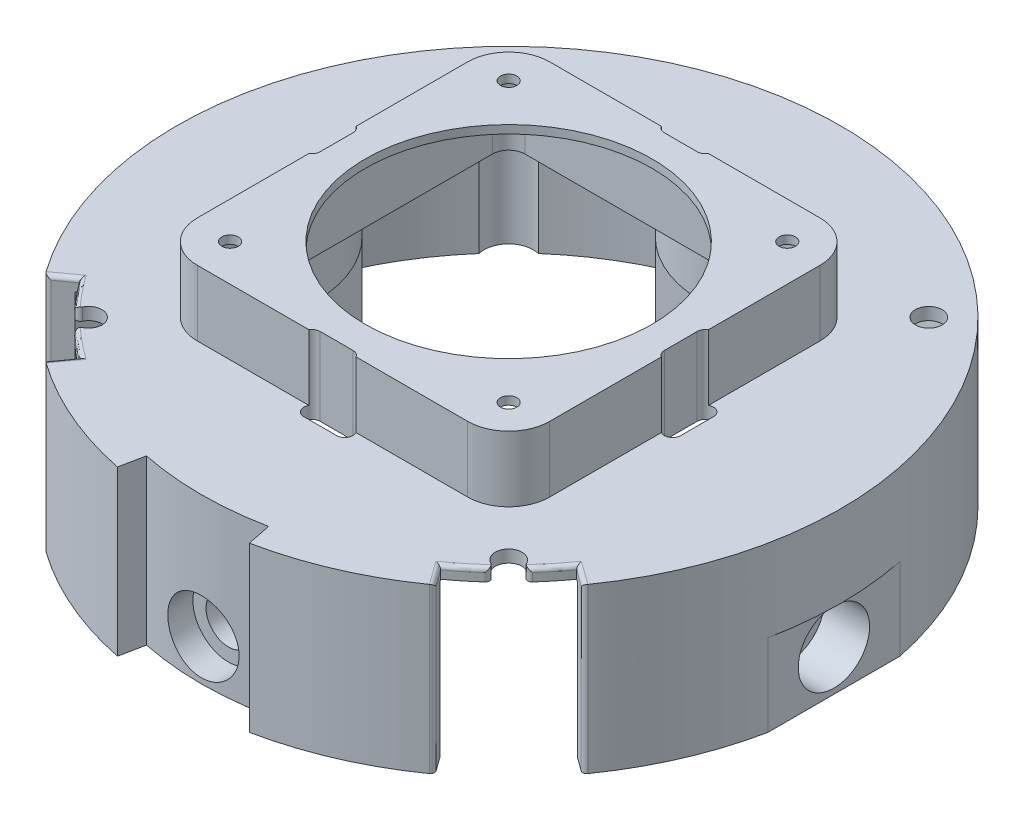
SolidWorks part; units mm, degrees
ref_plane "Front" through (0, 0, 0) normal (0, 0, 1) x (1, 0, 0)
ref_plane "Top" through (0, 0, 0) normal (0, 1, 0) x (1, 0, 0)
ref_plane "Right" through (0, 0, 0) normal (1, 0, 0) x (0, 0, -1)
sketch "Sketch1" plane through (0, 0, 0) normal (0, 1, 0) x (1, 0, 0)
  circle A0 centre (0, 0) radius 41.9
  dimension "D1" = 83.8
extrude "Top-Part" add sketch "Sketch1" along normal blind 15
sketch "Sketch2" plane through (0, 15, 0) normal (0, 1, 0) x (1, 0, 0)
  circle A0 centre (0, 0) radius 30
  dimension "D1" = 60
extrude "Cut-Extrude1" cut sketch "Sketch2" against normal blind 20
fillet "Fillet1" radius 1.5 1 edges at (0, 15, 41.9)
chamfer "Chamfer1" distance 2 angle 45 1 edges at (0, 15, 30)
sketch "Sketch8" plane through (0, 15, 0) normal (0, 1, 0) x (1, 0, 0)
  line L0 (0, 0) -> (0, 52.711) construction
  line L1 (25.0832, 22.5168) -> (28.0563, 23.5989)
  line L8 (0, 0) -> (-43.3951, 43.3951) construction
  line L9 (-25.6326, 25.6326) -> (-25.6326, 34.5059) construction
  line L10 (-22.5168, 25.0832) -> (-23.5989, 28.0563)
  line L11 (-23.5989, 28.0563) -> (-26.7147, 28.6057)
  line L12 (-26.7147, 28.6057) -> (-28.7485, 26.182)
  line L13 (-28.7485, 26.182) -> (-27.6663, 23.2089)
  line L14 (-27.6663, 23.2089) -> (-24.5505, 22.6595)
  line L15 (-24.5505, 22.6595) -> (-22.5168, 25.0832)
  line L16 (28.0563, 23.5989) -> (28.6057, 26.7147)
  line L17 (28.6057, 26.7147) -> (26.182, 28.7485)
  line L18 (26.182, 28.7485) -> (23.2089, 27.6663)
  line L19 (23.2089, 27.6663) -> (22.6595, 24.5505)
  line L20 (22.6595, 24.5505) -> (25.0832, 22.5168)
  line L21 (0, 0) -> (43.3951, 43.3951) construction
  line L23 (22.5168, -25.0832) -> (23.5989, -28.0563)
  line L24 (23.5989, -28.0563) -> (26.7147, -28.6057)
  line L25 (26.7147, -28.6057) -> (28.7485, -26.182)
  line L26 (28.7485, -26.182) -> (27.6663, -23.2089)
  line L27 (27.6663, -23.2089) -> (24.5505, -22.6595)
  line L28 (24.5505, -22.6595) -> (22.5168, -25.0832)
  line L29 (0, 0) -> (43.3951, -43.3951) construction
  line L31 (-25.0832, -22.5168) -> (-28.0563, -23.5989)
  line L32 (-28.0563, -23.5989) -> (-28.6057, -26.7147)
  line L33 (-28.6057, -26.7147) -> (-26.182, -28.7485)
  line L34 (-26.182, -28.7485) -> (-23.2089, -27.6663)
  line L35 (-23.2089, -27.6663) -> (-22.6595, -24.5505)
  line L36 (-22.6595, -24.5505) -> (-25.0832, -22.5168)
  line L37 (0, 0) -> (-43.3951, -43.3951) construction
  line L39 (-25.6326, 25.6326) -> (-27.9138, 12.6954) construction
  circle A0 centre (0, 0) radius 36.25 construction
  circle A1 centre (25.6326, 25.6326) radius 2.74 construction
  circle A2 centre (-25.6326, 25.6326) radius 2.74 construction
  circle A3 centre (25.6326, -25.6326) radius 2.74 construction
  circle A4 centre (-25.6326, -25.6326) radius 2.74 construction
  circle A5 centre (-25.6326, 25.6326) radius 1.625
  circle A6 centre (25.6326, 25.6326) radius 1.625
  circle A7 centre (25.6326, -25.6326) radius 1.625
  circle A8 centre (-25.6326, -25.6326) radius 1.625
  point P8 (25.6326, 25.6326)
  point P10 (28.331, 25.1568)
  point P18 (-25.6326, 25.6326)
  point P20 (-25.1568, 28.331)
  point P36 (25.6326, -25.6326)
  point P38 (25.1568, -28.331)
  point P50 (-25.6326, -25.6326)
  point P52 (-28.331, -25.1568)
  point P63 (0, 0)
  point P69 (-27.8231, 23.2366)
  dimension "D1" = 72.5
  dimension "D5" = 3.25
  dimension "D2" = 4
  dimension "D3" = 45
  dimension "D4" = 10
  dimension "D6" = 5.75
extrude "Cut-Extrude8" cut sketch "Sketch8<7>" against normal blind 3
sketch "Sketch8<7>" plane through (0, 15, 0) normal (0, 1, 0) x (1, 0, 0) same geometry as "Sketch8"
extrude "Cut-Extrude7" cut sketch "Sketch8" against normal through all contours A5 | A6 | A7 | A8
sketch "Sketch13" plane through (0, 0, 0) normal (0, -1, 0) x (1, 0, 0)
  line L0 (0, 0) -> (0, 66.0162) construction
  line L1 (-10, 35.5191) -> (-10, 40.6892)
  line L2 (10, 35.5191) -> (10, 40.6892)
  line L3 (-10, 40.6892) -> (10, 35.5191) construction
  line L4 (10, 40.6892) -> (-10, 35.5191) construction
  circle A0 centre (0, 0) radius 41.9 construction
  arc A1 (10, 40.6892) -> (-10, 40.6892) centre (0, 0) ccw
  arc A2 (10, 35.5191) -> (-10, 35.5191) centre (0, 0) ccw
  point P6 (0, 38.1042)
  point P10 (0, 36.9)
  point P12 (0, 41.9)
  dimension "D1" = 10
  dimension "D3" = 5
extrude "Cut-Extrude11" cut sketch "Sketch13" against normal through all
ref_plane "Plane2" through (0, 0, 41.9) normal (0, 0, 1) x (1, 0, 0)
ref_plane "Plane3" through (0, 0, 32.4) normal (0, 0, 1) x (1, 0, 0)
sketch "Sketch15" plane through (0, 0, 32.4) normal (0, 0, 1) x (1, 0, 0)
  line L0 (0, -23.0183) -> (0, 33.1182) construction
  circle A1 centre (0, 7.5) radius 1.625
  point P11 (0, 7.5)
  dimension "D3" = 3.25
  dimension "D1" = 7.5
extrude "Cut-Extrude14" cut sketch "Sketch15" against normal blind 10 and the other way blind 10
sketch "Sketch16" plane through (0, 0, 32.4) normal (0, 0, 1) x (1, 0, 0)
  line L0 (0, 0) -> (0, 26.985) construction
  line L2 (3.3775, 7.5) -> (1.6887, 10.425)
  line L3 (1.6887, 10.425) -> (-1.6887, 10.425)
  line L4 (-1.6887, 10.425) -> (-3.3775, 7.5)
  line L5 (-3.3775, 7.5) -> (-1.6887, 4.575)
  line L6 (-1.6887, 4.575) -> (1.6887, 4.575)
  line L7 (1.6887, 4.575) -> (3.3775, 7.5)
  circle A0 centre (0, 7.5) radius 2.925 construction
  point P4 (0, 4.575)
  point P13 (0, 10.425)
  dimension "D1" = 5.85
  dimension "D2" = 7.5
extrude "Cut-Extrude15" cut sketch "Sketch16" against normal blind 10
pattern_circular "CirPattern1" count 4 over 360 about axis through (0, 0, 0) along (0, 1, 0) of "Cut-Extrude14"
pattern_circular "CirPattern2" count 4 every 90 about axis through (0, 0, 0) along (0, 1, 0) of "Cut-Extrude15"
sketch "Sketch3" plane through (0, 0, 0) normal (0, -1, 0) x (1, 0, 0)
  circle A0 centre (0, 0) radius 41.9
  dimension "D1" = 83.8
extrude "Bottom-Part" add sketch "Sketch3" along normal blind 20 separate body
ref_plane "Plane1" through (0, -1.5, 0) normal (0, 1, 0) x (1, 0, 0)
sketch "Sketch6" plane through (0, -1.5, 0) normal (0, 1, 0) x (1, 0, 0)
  line L0 (0, 0) -> (-97.4577, 0) construction
  line L5 (-37.9, 0) -> (-41.9, 0) construction
  circle A0 centre (0, 0) radius 37.9
  circle A1 centre (0, 0) radius 41.9 construction
  circle A2 centre (0, 0) radius 41.9 construction
  point P6 (-37.9, 0)
  point P9 (-41.9, 0)
  dimension "D1" = 4
extrude "Cut-Extrude3" cut sketch "Sketch6" against normal through all
sketch "ｽｹｯﾁ1" plane through (0, 0, 0) normal (0, 1, 0) x (1, 0, 0)
  line L3 (21.5, -21.5) -> (-21.5, -21.5)
  line L4 (21.5, -21.5) -> (21.5, 21.5)
  line L5 (21.5, 21.5) -> (-21.5, 21.5)
  line L6 (-21.5, -21.5) -> (-21.5, 21.5)
  line L7 (21.5, -21.5) -> (-21.5, 21.5) construction
  line L8 (21.5, 21.5) -> (-21.5, -21.5) construction
  point P2 (0, 0)
  dimension "D1" = 43
extrude "ﾎﾞｽ - 押し出し1" add sketch "ｽｹｯﾁ1" along normal blind 8
fillet "ﾌｨﾚｯﾄ1" radius 5 4 edges at (21.5, 4, -21.5) (-21.5, 4, -21.5) (-21.5, 4, 21.5) (21.5, 4, 21.5)
sketch "Sketch7" plane through (0, -1.5, 0) normal (0, 1, 0) x (1, 0, 0)
  circle A0 centre (0, 0) radius 17.5
  circle A1 centre (17, -17) radius 1
  circle A2 centre (-17, -17) radius 1
  circle A3 centre (-17, 17) radius 1
  circle A4 centre (17, 17) radius 1
  dimension "D1" = 35
  dimension "D2" = 2
extrude "Cut-Extrude4" cut sketch "Sketch7" against normal through all and the other way through all
sketch "Sketch12" plane through (0, -1.5, 0) normal (0, -1, 0) x (1, 0, 0)
  line L1 (19.75, -19.75) -> (-19.75, -19.75)
  line L2 (19.75, -19.75) -> (19.75, 19.75)
  line L3 (19.75, 19.75) -> (-19.75, 19.75)
  line L4 (-19.75, -19.75) -> (-19.75, 19.75)
  line L5 (19.75, -19.75) -> (-19.75, 19.75) construction
  line L6 (19.75, 19.75) -> (-19.75, -19.75) construction
  point P0 (0, 0)
  dimension "D1" = 39.5
extrude "Cut-Extrude10" cut sketch "Sketch12" against normal blind 8.5
fillet "Fillet3" radius 2 4 edges at (-19.75, 2.75, -19.75) (-19.75, 2.75, 19.75) (19.75, 2.75, -19.75) (19.75, 2.75, 19.75)
sketch "Sketch17" plane through (0, -1.5, 0) normal (0, -1, 0) x (1, 0, 0)
  circle A0 centre (25.6326, -25.6326) radius 1.625 construction
  circle A1 centre (-25.6326, -25.6326) radius 1.625 construction
  circle A2 centre (25.6326, 25.6326) radius 1.625 construction
  circle A3 centre (-25.6326, 25.6326) radius 1.625 construction
  circle A4 centre (25.6326, -25.6326) radius 1.625
  circle A5 centre (-25.6326, -25.6326) radius 1.625
  circle A6 centre (25.6326, 25.6326) radius 1.625
  circle A7 centre (-25.6326, 25.6326) radius 1.625
extrude "Cut-Extrude16" cut sketch "Sketch17" against normal through all
sketch "Sketch18" plane through (0, -1.5, 0) normal (0, -1, 0) x (1, 0, 0)
  circle A0 centre (-25.6326, 25.6326) radius 3
  circle A1 centre (25.6326, 25.6326) radius 3
  circle A2 centre (25.6326, -25.6326) radius 3
  circle A3 centre (-25.6326, -25.6326) radius 3
  dimension "D1" = 6
extrude "Cut-Extrude17" cut sketch "Sketch18" along normal through all
sketch "Sketch19" plane through (0, -1.5, 0) normal (0, -1, 0) x (1, 0, 0)
  arc A1 (35.4434, 13.423) -> (35.4434, -13.423) centre (37, 0) ccw
  arc A2 (35.4434, -13.423) -> (35.4434, 13.423) centre (0, 0) ccw
  arc A14 (-13.423, 35.4434) -> (13.423, 35.4434) centre (0, 37) ccw
  arc A15 (24.9276, 28.5486) -> (-24.9276, 28.5486) centre (0, 0) ccw construction
  arc A16 (13.423, 35.4434) -> (-13.423, 35.4434) centre (0, 0) ccw
  arc A17 (13.423, -35.4434) -> (-13.423, -35.4434) centre (0, -37) ccw
  arc A18 (-13.423, -35.4434) -> (13.423, -35.4434) centre (0, 0) ccw
  arc A19 (-35.4434, -13.423) -> (-35.4434, 13.423) centre (-37, 0) ccw
  arc A20 (-35.4434, 13.423) -> (-35.4434, -13.423) centre (0, 0) ccw
  dimension "D1" = 37
  dimension "D2" = 4
extrude "Boss-Extrude1" add sketch "Sketch19" along normal blind 8.5
sketch "Sketch23" plane through (0, -10, 0) normal (0, -1, 0) x (1, 0, 0)
  line L1 (9.7077, -27.6) -> (-9.7077, -27.6)
  line L2 (27.6, -9.7077) -> (27.6, 9.7077)
  line L3 (9.7077, 27.6) -> (-9.7077, 27.6)
  line L4 (-27.6, -9.7077) -> (-27.6, 9.7077)
  line L5 (27.6, -27.6) -> (-27.6, 27.6) construction
  line L6 (27.6, 27.6) -> (-27.6, -27.6) construction
  arc A0 (-13.423, -35.4434) -> (13.423, -35.4434) centre (0, 0) ccw construction
  arc A1 (-28.5486, 24.9276) -> (-28.5486, -24.9276) centre (0, 0) ccw construction
  arc A2 (13.423, 35.4434) -> (-13.423, 35.4434) centre (0, 0) ccw construction
  arc A3 (35.4434, -13.423) -> (35.4434, 13.423) centre (0, 0) ccw construction
  arc A4 (35.4434, 13.423) -> (35.4434, -13.423) centre (37, 0) ccw construction
  arc A5 (13.423, -35.4434) -> (-13.423, -35.4434) centre (0, -37) ccw construction
  arc A6 (-35.4434, -13.423) -> (-35.4434, 13.423) centre (-37, 0) ccw construction
  arc A7 (-13.423, 35.4434) -> (13.423, 35.4434) centre (0, 37) ccw construction
  arc A8 (-13.423, -35.4434) -> (13.423, -35.4434) centre (0, 0) ccw
  arc A9 (-35.4434, 13.423) -> (-35.4434, -13.423) centre (0, 0) ccw
  arc A10 (13.423, 35.4434) -> (-13.423, 35.4434) centre (0, 0) ccw
  arc A11 (35.4434, -13.423) -> (35.4434, 13.423) centre (0, 0) ccw
  arc A12 (35.4434, 13.423) -> (27.6, 9.7077) centre (37, 0) ccw
  arc A13 (13.423, -35.4434) -> (9.7077, -27.6) centre (0, -37) ccw
  arc A14 (-35.4434, -13.423) -> (-27.6, -9.7077) centre (-37, 0) ccw
  arc A15 (-13.423, 35.4434) -> (-9.7077, 27.6) centre (0, 37) ccw
  arc A16 (27.6, -9.7077) -> (35.4434, -13.423) centre (37, 0) ccw
  arc A17 (9.7077, 27.6) -> (13.423, 35.4434) centre (0, 37) ccw
  arc A18 (-27.6, 9.7077) -> (-35.4434, 13.423) centre (-37, 0) ccw
  arc A19 (-9.7077, -27.6) -> (-13.423, -35.4434) centre (0, -37) ccw
  point P0 (0, 0)
  dimension "D1" = 55.2
  dimension "D2" = 55.2
extrude "Boss-Extrude2" add sketch "Sketch23" along normal blind 10
sketch "Sketch27" plane through (0, -20, 0) normal (0, -1, 0) x (1, 0, 0)
  line L0 (39.6917, 13.423) -> (39.6917, -13.423)
  line L1 (-13.423, 39.6917) -> (13.423, 39.6917)
  line L2 (13.423, -39.6917) -> (-13.423, -39.6917)
  line L3 (-39.6917, -13.423) -> (-39.6917, 13.423)
  circle A0 centre (0, 0) radius 41.9 construction
  arc A1 (13.423, 39.6917) -> (-13.423, 39.6917) centre (0, 0) ccw
  arc A2 (39.6917, -13.423) -> (39.6917, 13.423) centre (0, 0) ccw
  arc A3 (-13.423, -39.6917) -> (13.423, -39.6917) centre (0, 0) ccw
  arc A4 (-39.6917, 13.423) -> (-39.6917, -13.423) centre (0, 0) ccw
  dimension "D1" = 4
extrude "Cut-Extrude18" cut sketch "Sketch27" against normal blind 10
sketch "Sketch28" plane through (0, 0, 39.6917) normal (0, 0, 1) x (1, 0, 0)
  line L0 (-13.423, -20) -> (13.423, -20) construction
  circle A0 centre (0, -15) radius 2.75
  dimension "D1" = 5.5
  dimension "D2" = 5
extrude "Cut-Extrude19" cut sketch "Sketch28" against normal blind 13
sketch "Sketch29" plane through (0, 0, 39.6917) normal (0, 0, 1) x (1, 0, 0)
  circle A0 centre (0, -15) radius 4.35
extrude "Cut-Extrude20" cut sketch "Sketch29" against normal blind 5.5
pattern_circular "CirPattern3" count 4 over 360 about axis through (0, -20, 0) along (0, -1, 0) of "Cut-Extrude19", "Cut-Extrude20"
sketch "Sketch30" plane through (0, 15, 0) normal (0, 1, 0) x (1, 0, 0)
  line L0 (-10, -39.1428) -> (-10, -35.5191) construction
  line L1 (-10, -44.1135) -> (10, -44.1135)
  line L2 (-10, -44.1135) -> (-10, -34.9)
  line L3 (-10, -34.9) -> (10, -34.9)
  line L4 (10, -44.1135) -> (10, -34.9)
  dimension "D1" = 34.9
extrude "Cut-Extrude21" cut sketch "Sketch30" against normal up to surface (15 mm away) up to face at (-25.6326, 0, -27.2576)
sketch "Sketch31" plane through (0, 15, 0) normal (0, 1, 0) x (1, 0, 0)
  circle A0 centre (0, 0) radius 30
  circle A1 centre (0, 0) radius 41.9
extrude "Cut-Extrude22" cut sketch "Sketch31" against normal up to surface (15 mm away) up to face at (0, 0, -41.9)
sketch "Sketch32" plane through (0, -20, 0) normal (0, -1, 0) x (1, 0, 0)
  circle A0 centre (0, 0) radius 40.5
  circle A1 centre (0, 0) radius 43.059
  dimension "D1" = 81
extrude "Cut-Extrude23" cut sketch "Sketch32" against normal through all
sketch "Sketch33" plane through (0, -20, 0) normal (0, -1, 0) x (1, 0, 0)
  line L0 (0, 0) -> (-25.6326, 25.6326) construction
  line L1 (-22.0419, 30.3381) -> (-23.8053, 32.7652)
  line L2 (-30.3381, 22.0419) -> (-32.7652, 23.8053)
  line L3 (0, 0) -> (0, 40.5) construction
  line L4 (7.4545, 36.7516) -> (8.0509, 39.6917)
  line L5 (-7.4545, 36.7516) -> (-8.0509, 39.6917)
  line L6 (22.0419, 30.3381) -> (23.8053, 32.7652)
  line L7 (30.3381, 22.0419) -> (32.7652, 23.8053)
  arc A0 (-23.8053, 32.7652) -> (-32.7652, 23.8053) centre (0, 0) ccw
  arc A1 (-22.0419, 30.3381) -> (-30.3381, 22.0419) centre (0, 0) ccw
  arc A2 (8.0509, 39.6917) -> (-8.0509, 39.6917) centre (0, 0) ccw
  arc A3 (7.4545, 36.7516) -> (-7.4545, 36.7516) centre (0, 0) ccw
  arc A4 (23.8053, 32.7652) -> (32.7652, 23.8053) centre (0, 0) cw
  arc A5 (22.0419, 30.3381) -> (30.3381, 22.0419) centre (0, 0) cw
  dimension "D2" = 3
  dimension "D3" = 9
extrude "Cut-Extrude24" cut sketch "Sketch33" against normal through all
fillet "Fillet4" radius 0.5 16 edges at (32.7652, -10, 23.8053) (31.5517, 0, 22.9236) (28.8553, 0, 23.9504) (27.2527, -0.75, 25.7593) (25.7593, -0.75, 27.2527) (23.9504, 0, 28.8553) (22.9236, 0, 31.5517) (23.8053, -10, 32.7652) (-25.7593, -0.75, 27.2527) (-27.2527, -0.75, 25.7593) (-22.9236, 0, 31.5517) (-23.9504, 0, 28.8553) (-28.8553, 0, 23.9504) (-31.5517, 0, 22.9236) (-23.8053, -10, 32.7652) (-32.7652, -10, 23.8053)
sketch "Sketch34" plane through (0, -1.5, 0) normal (0, -1, 0) x (1, 0, 0)
  line L0 (0, 46.8677) -> (0, -59.3496) construction
  line L1 (23, 2) -> (23, -2)
  line L2 (21, 2) -> (21, -2)
  line L3 (-2, 23) -> (2, 23)
  line L4 (-2, 21) -> (2, 21)
  line L5 (2, -23) -> (-2, -23)
  line L6 (2, -21) -> (-2, -21)
  line L7 (-23, -2) -> (-23, 2)
  line L8 (-21, -2) -> (-21, 2)
  line L9 (0, 0) -> (2, 21) construction
  arc A0 (-2, 23) -> (-2, 21) centre (-2, 22) ccw
  arc A1 (2, 21) -> (2, 23) centre (2, 22) ccw
  arc A8 (23, 2) -> (21, 2) centre (22, 2) ccw
  arc A9 (21, -2) -> (23, -2) centre (22, -2) ccw
  arc A10 (2, -23) -> (2, -21) centre (2, -22) ccw
  arc A11 (-2, -21) -> (-2, -23) centre (-2, -22) ccw
  arc A12 (-23, -2) -> (-21, -2) centre (-22, -2) ccw
  arc A13 (-21, 2) -> (-23, 2) centre (-22, 2) ccw
  dimension "D1" = 2
  dimension "D2" = 2
  dimension "D3" = 4
  dimension "D4" = 22
  dimension "D6" = 21.095
  dimension "D5" = 4
extrude "Cut-Extrude25" cut sketch "Sketch34" against normal through all
